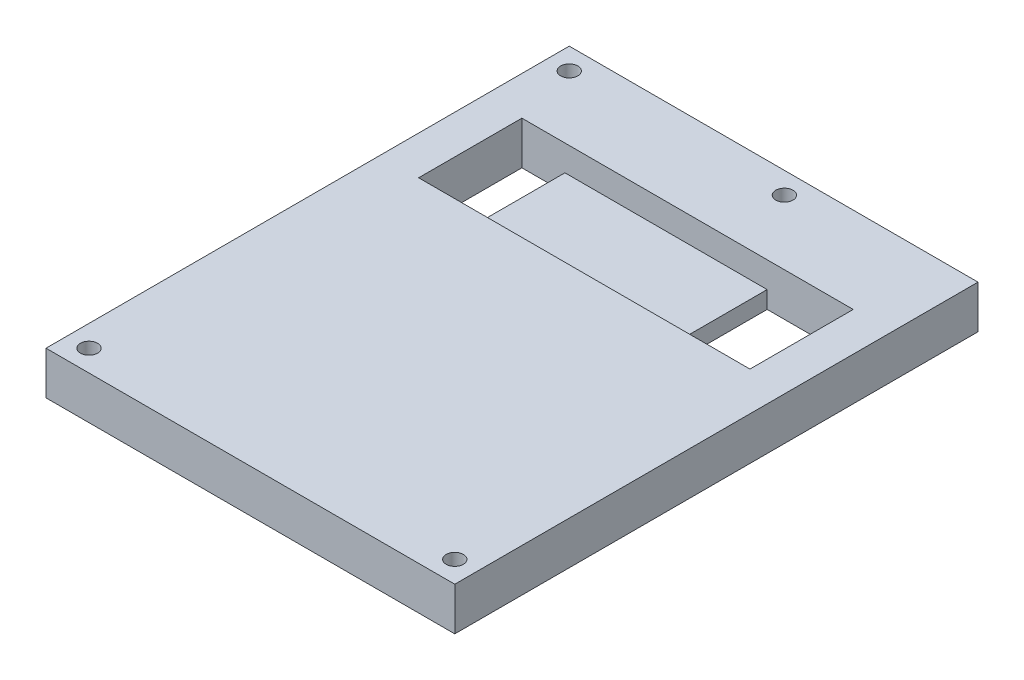
SolidWorks part; units mm, degrees
ref_plane "前视基准面" through (0, 0, 0) normal (0, 0, 1) x (1, 0, 0)
ref_plane "上视基准面" through (0, 0, 0) normal (0, 1, 0) x (1, 0, 0)
ref_plane "右视基准面" through (0, 0, 0) normal (1, 0, 0) x (0, 0, -1)
other "Configuration Table"
sketch "草图1" plane through (0, 0, 0) normal (0, 1, 0) x (1, 0, 0)
  line L1 (-54.4053, 33.3382) -> (-6.9053, 33.3382)
  line L2 (-54.4053, 33.3382) -> (-54.4053, -27.4618)
  line L3 (-54.4053, -27.4618) -> (-6.9053, -27.4618)
  line L4 (-6.9053, 33.3382) -> (-6.9053, -27.4618)
  line L5 (-54.4053, 33.3382) -> (-49.4053, 33.3382) construction
  line L6 (-54.4053, 33.3382) -> (-54.4053, 23.3382) construction
  dimension "D1" = 47.5
  dimension "D2" = 60.8
extrude "凸台-拉伸1" add sketch "草图1" against normal blind 5 contours L4 L3 L2 L1
sketch "草图2" plane through (0, 0, 0) normal (0, 1, 0) x (1, 0, 0)
  line L0 (-54.4053, 33.3382) -> (-54.4053, -27.4618) construction
  line L1 (-49.9053, 23.3382) -> (-11.4053, 23.3382)
  line L2 (-49.9053, 23.3382) -> (-49.9053, 11.3382)
  line L3 (-49.9053, 11.3382) -> (-11.4053, 11.3382)
  line L4 (-11.4053, 23.3382) -> (-11.4053, 11.3382)
  line L5 (-54.4053, 33.3382) -> (-6.9053, 33.3382) construction
  dimension "D1" = 4.5
  dimension "D2" = 10
  dimension "D3" = 12
  dimension "D4" = 38.5
extrude "切除-拉伸1" cut sketch "草图2" against normal blind 3 contours L2 L3 L4 L1
sketch "草图3" plane through (0, -3, 0) normal (0, 1, 0) x (1, 0, 0)
  line L0 (-49.9053, 11.3382) -> (-11.4053, 11.3382) construction
  line L3 (-49.9053, 23.3382) -> (-44.9053, 23.3382)
  line L4 (-49.9053, 23.3382) -> (-49.9053, 11.3382)
  line L5 (-49.9053, 11.3382) -> (-44.9053, 11.3382)
  line L6 (-44.9053, 23.3382) -> (-44.9053, 11.3382)
  line L7 (-49.9053, 11.3382) -> (-11.4053, 11.3382) construction
  line L8 (-11.4053, 23.3382) -> (-21.4053, 23.3382)
  line L9 (-11.4053, 23.3382) -> (-11.4053, 11.3382)
  line L10 (-11.4053, 11.3382) -> (-21.4053, 11.3382)
  line L11 (-21.4053, 23.3382) -> (-21.4053, 11.3382)
  dimension "D1" = 5
  dimension "D2" = 10
extrude "切除-拉伸2" cut sketch "草图3" against normal blind 2
sketch "草图4" plane through (0, 0, 0) normal (0, 1, 0) x (1, 0, 0)
  line L0 (-6.9053, 33.3382) -> (-6.9053, -27.4618) construction
  line L3 (-54.4053, -27.4618) -> (-6.9053, -27.4618) construction
  line L4 (-54.4053, 33.3382) -> (-54.4053, -27.4618) construction
  line L5 (-54.4053, 33.3382) -> (-6.9053, 33.3382) construction
  circle A0 centre (-9.4053, -24.9618) radius 1
  circle A1 centre (-51.9053, -24.9618) radius 1
  circle A2 centre (-51.9053, 30.8382) radius 1
  circle A3 centre (-26.9053, 30.8382) radius 1
  dimension "D1" = 2.5
  dimension "D3" = 2.5
  dimension "D5" = 2.5
  dimension "D7" = 20
  dimension "D2" = 2.5
  dimension "D4" = 2.5
  dimension "D6" = 2.5
  dimension "D8" = 2.5
extrude "切除-拉伸3" cut sketch "草图4" against normal blind 5
